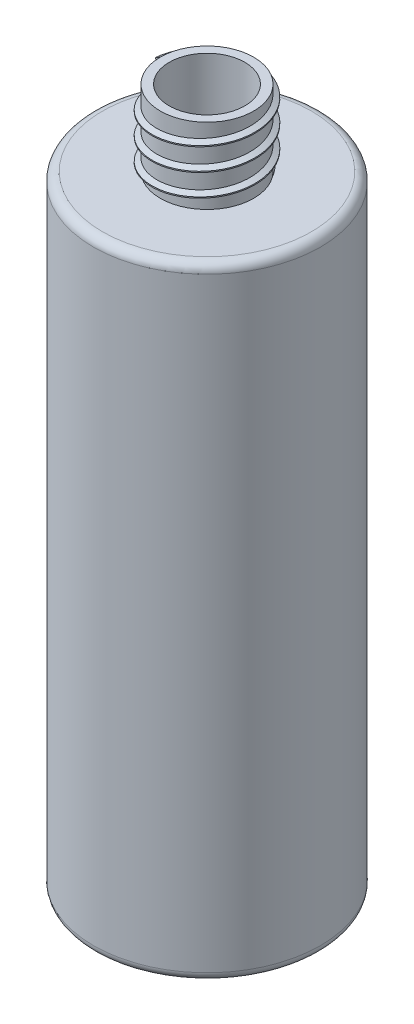
SolidWorks part; units mm, degrees
ref_plane "Ön Düzlem" through (0, 0, 0) normal (0, 0, 1) x (1, 0, 0)
ref_plane "Üst Düzlem" through (0, 0, 0) normal (0, 1, 0) x (1, 0, 0)
ref_plane "Sağ Düzlem" through (0, 0, 0) normal (1, 0, 0) x (0, 0, -1)
sketch "Çizim1" plane through (0, 0, 0) normal (0, 0, 1) x (1, 0, 0)
  line L0 (0, 0) -> (0, 157) construction
  line L1 (0, 0) -> (-25.5, 0)
  line L2 (-25.5, 0) -> (-25.5, 140)
  line L3 (-25.5, 140) -> (-10.5, 140)
  line L4 (-10.5, 140) -> (-10.5, 157)
  line L5 (-10.5, 157) -> (0, 157)
  line L6 (0, 0) -> (0, 157)
  dimension "D1" = 51
  dimension "D2" = 21
  dimension "D3" = 140
  dimension "D4" = 17
revolve "Döndür1" add sketch "Çizim1" angle 360 about L0
shell "İç Boşaltma1" thickness 2 removed face at (0, 157, -10.5)
fillet "Radyus1" radius 2 2 edges at (0, 140, -25.5) (0, 0, -25.5)
thread "Diş1" pitch 2 method extrude profile "Diş Profili1" start angle 0, offset 0, length 0, pitch 5, diameter 21
ref_plane "Düzlem1" through (-10.5, 157, 0) normal (0, 0, 1) x (-1, 0, 0)
sketch "Diş Profili1" plane through (-10.5, 157, 0) normal (0, 0, 1) x (-1, 0, 0)
  line L0 (0, 0) -> (0, 2) construction
  line L1 (0, 0) -> (1.0825, 0.625)
  line L2 (1.0825, 0.625) -> (1.0825, 0.875)
  line L3 (1.0825, 0.875) -> (0, 1.5)
  line L4 (1.0825, 0.75) -> (0, 0.75) construction
  line L11 (0, 0) -> (0, 1.5)
  point P2 (0, 0)
  dimension "Pitch" = 2
  dimension "Profile_Angle" = 60
  dimension "Profile_Land" = 0.25
  dimension "Profile_Height" = 1.0825
